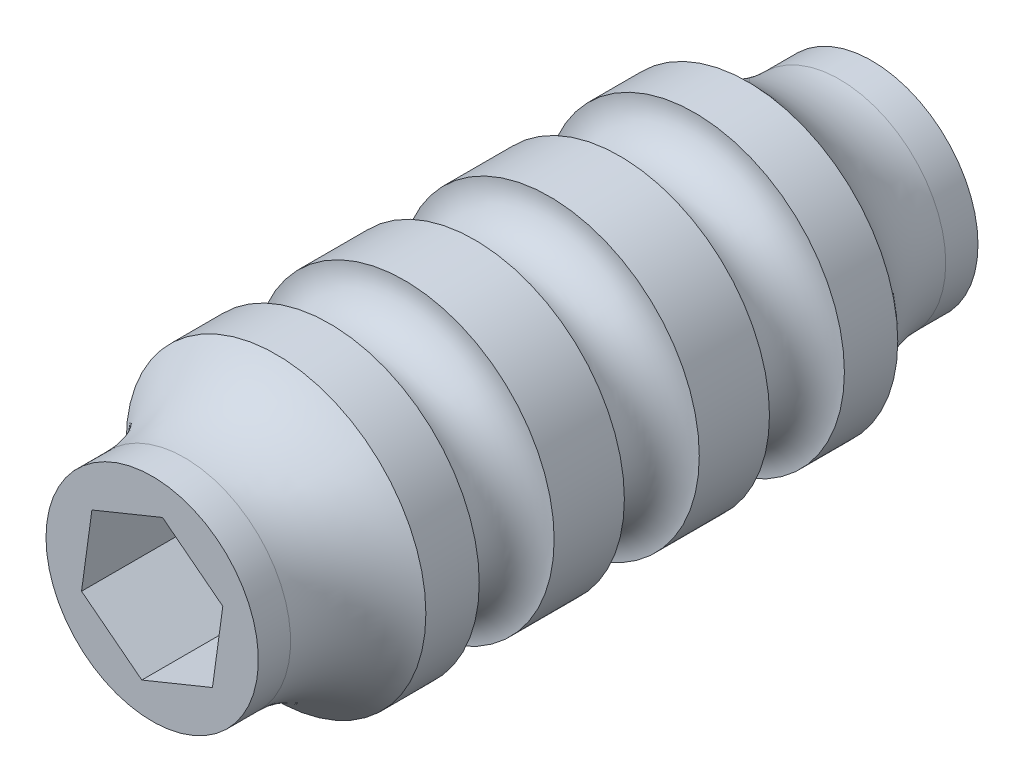
SolidWorks part; units mm, degrees
ref_plane "Front Plane" through (0, 0, 0) normal (0, 0, 1) x (1, 0, 0)
ref_plane "Top Plane" through (0, 0, 0) normal (0, 1, 0) x (1, 0, 0)
ref_plane "Right Plane" through (0, 0, 0) normal (1, 0, 0) x (0, 0, -1)
sketch "Sketch1" plane through (0, 0, 0) normal (0, 1, 0) x (1, 0, 0)
  line L1 (4, 0) -> (12.7, 0)
  line L2 (0, 0) -> (0, 40) construction
  line L3 (4, 40) -> (12.7, 40)
  line L8 (4, 0) -> (4, 40)
  line L11 (12.7, 0) -> (12.7, 4.525)
  line L12 (12.7, 35.475) -> (12.7, 40)
  line L13 (12.7, 10.875) -> (12.7, 13.0154)
  line L14 (12.7, 26.9846) -> (12.7, 29.125)
  line L17 (12.7, 26.9846) -> (12.7, 23.175)
  line L18 (12.7, 16.825) -> (12.7, 13.0154)
  arc A1 (12.7, 35.475) -> (12.7, 29.125) centre (12.7, 32.3) ccw
  arc A2 (12.7, 10.875) -> (12.7, 4.525) centre (12.7, 7.7) ccw
  arc A6 (12.7, 23.175) -> (12.7, 16.825) centre (12.7, 20) ccw
  dimension "D3" = 6.35
  dimension "D4" = 4
  dimension "D1" = 40
  dimension "D2" = 12.7
  dimension "D5" = 24.6
revolve "Revolve1" add sketch "Sketch1" angle 360 about L2
sketch "Sketch2" plane through (0, 0, -40) normal (0, 0, -1) x (-1, 0, 0)
  line L1 (-0.878, 6.4064) -> (-5.9871, 2.4428)
  line L2 (-5.9871, 2.4428) -> (-5.1091, -3.9636)
  line L3 (-5.1091, -3.9636) -> (0.878, -6.4064)
  line L4 (0.878, -6.4064) -> (5.9871, -2.4428)
  line L5 (5.9871, -2.4428) -> (5.1091, 3.9636)
  line L6 (5.1091, 3.9636) -> (-0.878, 6.4064)
  circle A0 centre (0, 0) radius 5.6 construction
  dimension "D1" = 11.2
extrude "Cut-Extrude1" cut sketch "Sketch2" against normal through all
sketch "Sketch3" plane through (0, 0, -40) normal (0, 0, -1) x (-1, 0, 0)
  line L6 (5.1091, 3.9636) -> (-0.878, 6.4064)
  line L7 (5.9871, -2.4428) -> (5.1091, 3.9636)
  line L8 (0.878, -6.4064) -> (5.9871, -2.4428)
  line L9 (-5.1091, -3.9636) -> (0.878, -6.4064)
  line L10 (-5.9871, 2.4428) -> (-5.1091, -3.9636)
  line L11 (-0.878, 6.4064) -> (-5.9871, 2.4428)
  line L12 (5.1091, 3.9636) -> (-0.878, 6.4064)
  line L13 (5.9871, -2.4428) -> (5.1091, 3.9636)
  line L14 (0.878, -6.4064) -> (5.9871, -2.4428)
  line L15 (-5.1091, -3.9636) -> (0.878, -6.4064)
  line L16 (-5.9871, 2.4428) -> (-5.1091, -3.9636)
  line L17 (-0.878, 6.4064) -> (-5.9871, 2.4428)
  circle A0 centre (0, 0) radius 9
  dimension "D2" = 18
  dimension "D1" = 0
extrude "Boss-Extrude1" add sketch "Sketch3" along normal blind 10.5
sketch "Sketch4" plane through (0, 0, 0) normal (0, 0, 1) x (1, 0, 0)
  line L6 (5.1091, -3.9636) -> (5.9871, 2.4428)
  line L7 (5.9871, 2.4428) -> (0.878, 6.4064)
  line L8 (0.878, 6.4064) -> (-5.1091, 3.9636)
  line L9 (-5.1091, 3.9636) -> (-5.9871, -2.4428)
  line L10 (-5.9871, -2.4428) -> (-0.878, -6.4064)
  line L11 (-0.878, -6.4064) -> (5.1091, -3.9636)
  line L12 (5.1091, -3.9636) -> (5.9871, 2.4428)
  line L13 (5.9871, 2.4428) -> (0.878, 6.4064)
  line L14 (0.878, 6.4064) -> (-5.1091, 3.9636)
  line L15 (-5.1091, 3.9636) -> (-5.9871, -2.4428)
  line L16 (-5.9871, -2.4428) -> (-0.878, -6.4064)
  line L17 (-0.878, -6.4064) -> (5.1091, -3.9636)
  circle A1 centre (0, 0) radius 9
  circle A2 centre (0, 0) radius 9
  dimension "D1" = 0
  dimension "D2" = 0
extrude "Boss-Extrude2" add sketch "Sketch4" along normal blind 10.5
fillet "Fillet1" radius 10 2 edges at (-9, 0, -40) (9, 0, 0)
fillet "Fillet2" radius 2 rebuild error yes
